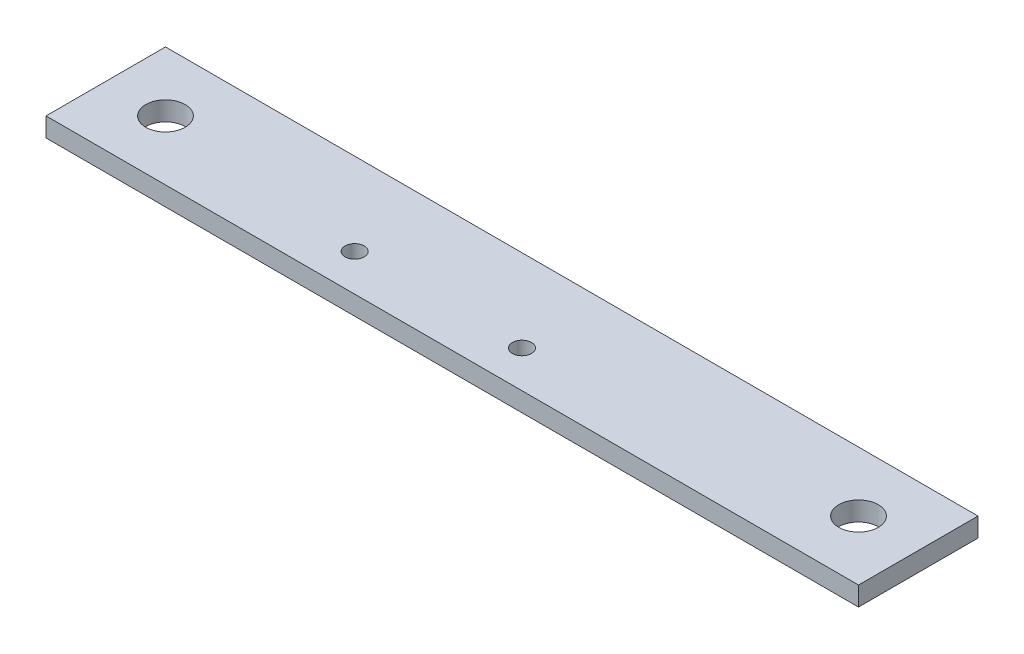
SolidWorks part; units mm, degrees
ref_plane "Front Plane" through (0, 0, 0) normal (0, 0, 1) x (1, 0, 0)
ref_plane "Top Plane" through (0, 0, 0) normal (0, 1, 0) x (1, 0, 0)
ref_plane "Right Plane" through (0, 0, 0) normal (1, 0, 0) x (0, 0, -1)
sketch "Sketch1" plane through (0, 0, 0) normal (0, 1, 0) x (1, 0, 0)
  line L1 (-85, 12.5) -> (85, 12.5)
  line L2 (-85, 12.5) -> (-85, -12.5)
  line L3 (-85, -12.5) -> (85, -12.5)
  line L4 (85, 12.5) -> (85, -12.5)
  line L5 (-85, 12.5) -> (85, -12.5) construction
  line L6 (-85, -12.5) -> (85, 12.5) construction
  circle A0 centre (-10.6801, 3.3392) radius 4.5
  circle A1 centre (-10.6585, -3.6607) radius 14
  circle A2 centre (-28.1585, -4.7634) radius 2
  circle A3 centre (6.8415, -4.7634) radius 2
  circle A4 centre (72.5, 0) radius 4.125
  point P0 (0, 0)
  point P17 (85, 0)
  dimension "D3" = 12.5
  dimension "D4" = 4
  dimension "D5" = 4
  dimension "D6" = 8.25
  dimension "D1" = 25
  dimension "D2" = 170
extrude "Boss-Extrude1" add sketch "Sketch1" along normal blind 4 contours A1 L3 L4 L1 L2 A4 A3 A2 | L3 A1 A0 | A0 region at (0, 0, -10.7817) region at (-10.6556, 0, 2.8007)
sketch "Sketch2" plane through (0, 4, 0) normal (0, 1, 0) x (1, 0, 0)
  line L0 (-85, 12.5) -> (-85, -12.5) construction
  circle A0 centre (-72.5, 0) radius 4.125
  circle A1 centre (-72.5, 0) radius 20 construction
  circle A2 centre (-42.5, 0) radius 10 construction
  dimension "D1" = 8.25
  dimension "D2" = 12.5
extrude "Cut-Extrude1" cut sketch "Sketch2" against normal through all
